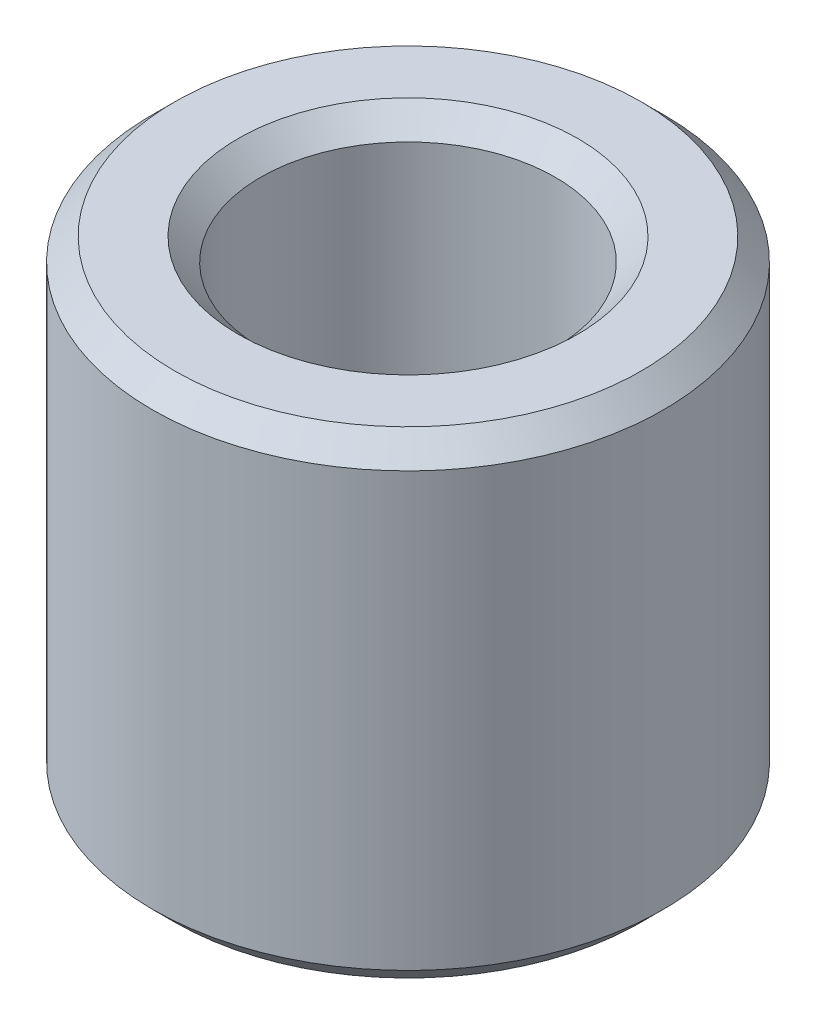
SolidWorks part; units mm, degrees
ref_plane "Front Plane" through (0, 0, 0) normal (0, 0, 1) x (1, 0, 0)
ref_plane "Top Plane" through (0, 0, 0) normal (0, 1, 0) x (1, 0, 0)
ref_plane "Right Plane" through (0, 0, 0) normal (1, 0, 0) x (0, 0, -1)
sketch "Sketch1" plane through (0, 0, 0) normal (0, 1, 0) x (1, 0, 0)
  circle A0 centre (0, 0) radius 37.5
  dimension "SLEEVE_OD" = 75
extrude "Boss-Extrude1" add sketch "Sketch1" along normal blind 70.0336
sketch "Sketch2" plane through (0, 0, 0) normal (0, 1, 0) x (1, 0, 0)
  circle A0 centre (0, 0) radius 21.6173
  dimension "BORE_D" = 43.2346
extrude "Cut-Extrude1" cut sketch "Sketch2" along normal through all
chamfer "Chamfer1" distance 3.2841 angle 45 4 edges at (0, 70.0336, 21.6173) (0, 0, 21.6173) (0, 0, 37.5) (0, 70.0336, 37.5)
